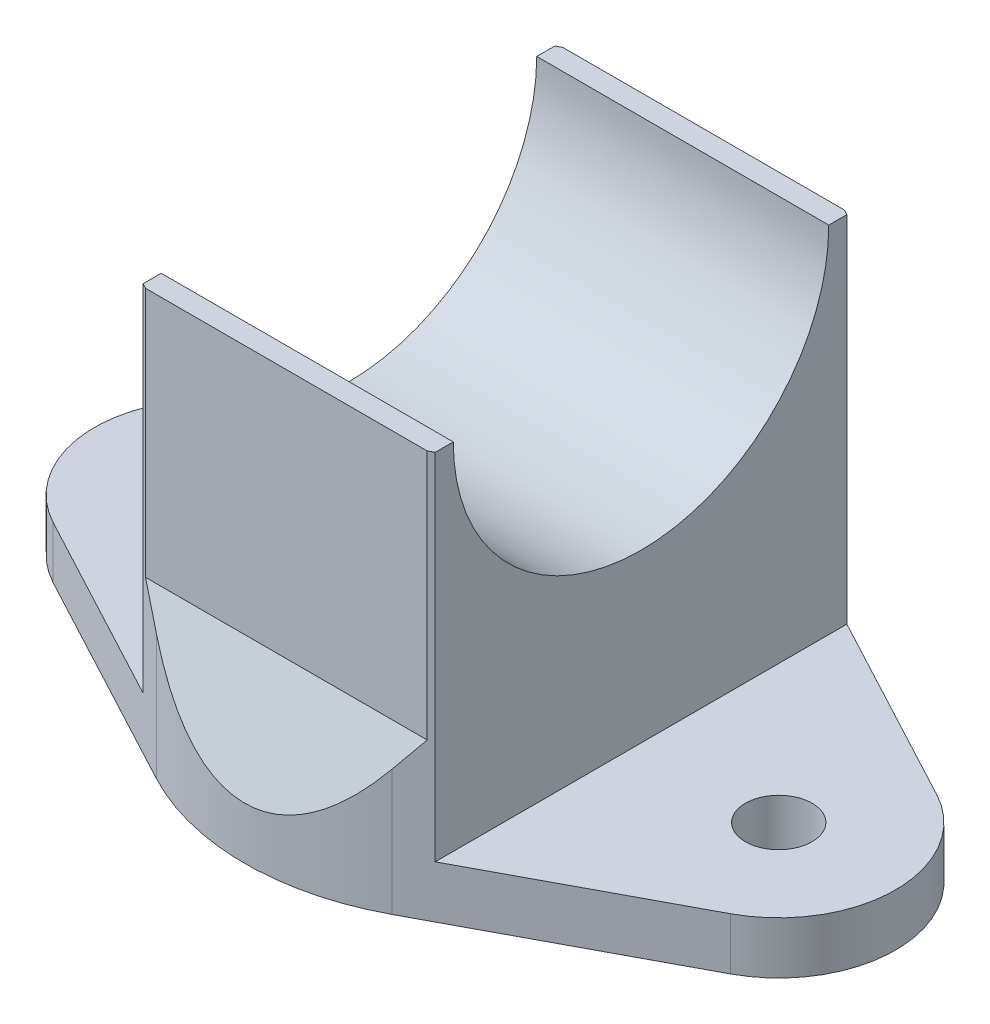
SolidWorks part; units mm, degrees
ref_plane "前视基准面" through (0, 0, 0) normal (0, 0, 1) x (1, 0, 0)
ref_plane "上视基准面" through (0, 0, 0) normal (0, 1, 0) x (1, 0, 0)
ref_plane "右视基准面" through (0, 0, 0) normal (1, 0, 0) x (0, 0, -1)
sketch "草图1" plane through (0, 0, 0) normal (0, 1, 0) x (1, 0, 0)
  line L1 (16.2353, -4.9412) -> (5.6471, -10.5882)
  line L2 (-16.2353, 4.9412) -> (-5.6471, 10.5882)
  line L3 (-16.2353, -4.9412) -> (-5.6471, -10.5882)
  line L4 (16.2353, 4.9412) -> (5.6471, 10.5882)
  circle A0 centre (-13.6, 0) radius 1.6
  circle A1 centre (13.6, 0) radius 1.6
  arc A2 (-16.2353, 4.9412) -> (-16.2353, -4.9412) centre (-13.6, 0) ccw
  arc A3 (16.2353, -4.9412) -> (16.2353, 4.9412) centre (13.6, 0) ccw
  arc A4 (-5.6471, -10.5882) -> (5.6471, -10.5882) centre (0, 0) ccw
  arc A5 (5.6471, 10.5882) -> (-5.6471, 10.5882) centre (0, 0) ccw
extrude "凸台-拉伸1" add sketch "草图1" against normal blind 2.5
sketch "草图2" plane through (0, 0, 0) normal (1, 0, 0) x (0, 0, -1)
  line L0 (12, 0) -> (-12, 0)
  line L1 (-10.5882, 0) -> (-12, 0) construction
  line L2 (-10, 5) -> (-10, 17)
  line L4 (-10, 5) -> (-12, 0)
  line L6 (10, 5) -> (12, 0)
  line L7 (10, 5) -> (10, 17)
  line L8 (-10, 17) -> (10, 17)
  point P7 (0, 0)
  point P11 (0, 0)
extrude "凸台-拉伸2" add sketch "草图2" along normal blind 7 and the other way blind 7
sketch "草图4" plane through (0, 0, 0) normal (0, 1, 0) x (1, 0, 0)
  line L0 (5.6471, -10.5882) -> (7, -9.8667) construction
  line L1 (-7, -9.8667) -> (-5.6471, -10.5882) construction
  line L2 (-5.6471, 10.5882) -> (-7, 9.8667) construction
  line L3 (7, 9.8667) -> (5.6471, 10.5882) construction
  line L4 (7, -9.8667) -> (16.2353, -4.9412) construction
  line L5 (16.2353, 4.9412) -> (7, 9.8667) construction
  line L6 (-7, 9.8667) -> (-16.2353, 4.9412) construction
  line L7 (-16.2353, -4.9412) -> (-7, -9.8667) construction
  line L8 (5.6471, -10.5882) -> (7, -9.8667)
  line L9 (-7, -9.8667) -> (-5.6471, -10.5882)
  line L10 (-5.6471, 10.5882) -> (-7, 9.8667)
  line L11 (7, 9.8667) -> (5.6471, 10.5882)
  line L12 (7, -9.8667) -> (16.2353, -4.9412)
  line L13 (16.2353, 4.9412) -> (7, 9.8667)
  line L14 (-7, 9.8667) -> (-16.2353, 4.9412)
  line L15 (-16.2353, -4.9412) -> (-7, -9.8667)
  arc A0 (0, -12) -> (5.6471, -10.5882) centre (0, 0) ccw construction
  arc A1 (-5.6471, -10.5882) -> (0, -12) centre (0, 0) ccw construction
  arc A2 (0, 12) -> (-5.6471, 10.5882) centre (0, 0) ccw construction
  arc A3 (5.6471, 10.5882) -> (0, 12) centre (0, 0) ccw construction
  arc A4 (16.2353, -4.9412) -> (16.2353, 4.9412) centre (13.6, 0) ccw construction
  arc A5 (-16.2353, 4.9412) -> (-16.2353, -4.9412) centre (-13.6, 0) ccw construction
  arc A6 (0, -12) -> (5.6471, -10.5882) centre (0, 0) ccw
  arc A7 (-5.6471, -10.5882) -> (0, -12) centre (0, 0) ccw
  arc A8 (0, 12) -> (-5.6471, 10.5882) centre (0, 0) ccw
  arc A9 (5.6471, 10.5882) -> (0, 12) centre (0, 0) ccw
  arc A10 (16.2353, -4.9412) -> (16.2353, 4.9412) centre (13.6, 0) ccw
  arc A11 (-16.2353, 4.9412) -> (-16.2353, -4.9412) centre (-13.6, 0) ccw
  circle A12 centre (0, 0) radius 25
extrude "切除-拉伸3" cut sketch "草图4" along normal through all
sketch "草图5" plane through (0, 0, 0) normal (0, 0, 1) x (1, 0, 0)
  line L0 (-6.75, 17) -> (6.75, 17) construction
  circle A0 centre (0, 17) radius 9
sketch "草图7" plane through (0, 0, 0) normal (1, 0, 0) x (0, 0, -1)
  line L0 (0, 26) -> (0, 8) construction
  circle A0 centre (0, 17) radius 9
extrude "切除-拉伸4" cut sketch "草图7" against normal blind 10 and the other way blind 10
